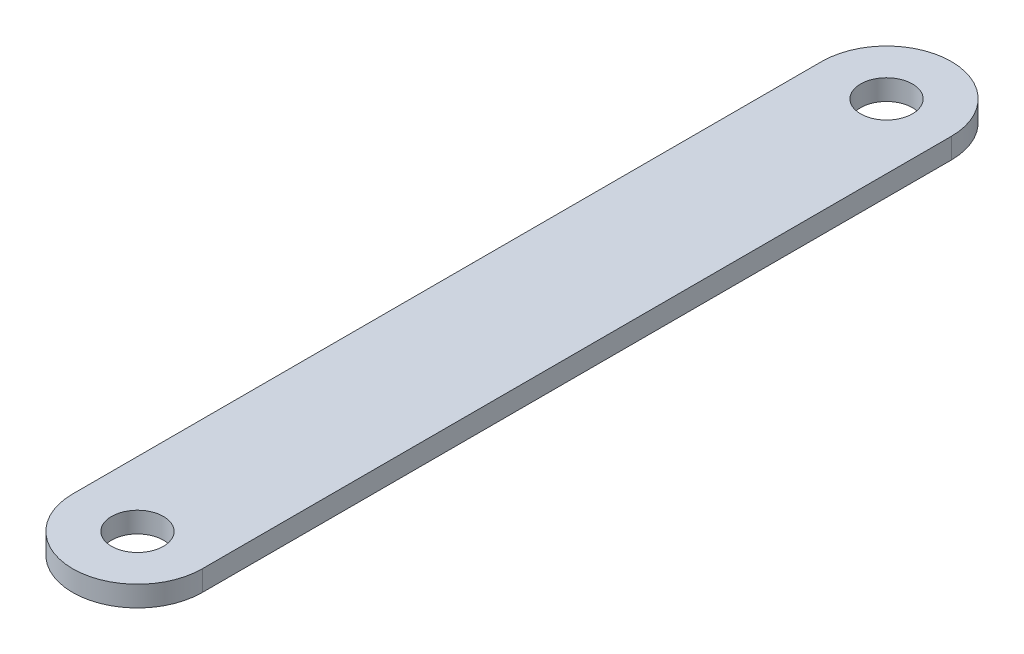
SolidWorks part; units mm, degrees
ref_plane "Front Plane" through (0, 0, 0) normal (0, 0, 1) x (1, 0, 0)
ref_plane "Top Plane" through (0, 0, 0) normal (0, 1, 0) x (1, 0, 0)
ref_plane "Right Plane" through (0, 0, 0) normal (1, 0, 0) x (0, 0, -1)
sketch "Sketch2" plane through (0, 0, 0) normal (0, 1, 0) x (1, 0, 0)
  line L0 (-5, 57.8) -> (-5, 0)
  line L1 (5, 57.8) -> (5, 0)
  circle A0 centre (0, 0) radius 2
  circle A1 centre (0, 57.8) radius 2
  arc A2 (5, 0) -> (-5, 0) centre (0, 0) cw
  arc A3 (5, 57.8) -> (-5, 57.8) centre (0, 57.8) ccw
  dimension "D2" = 4
  dimension "D3" = 5
  dimension "D1" = 57.8
extrude "Boss-Extrude1" add sketch "Sketch2" along normal blind 1.5875
